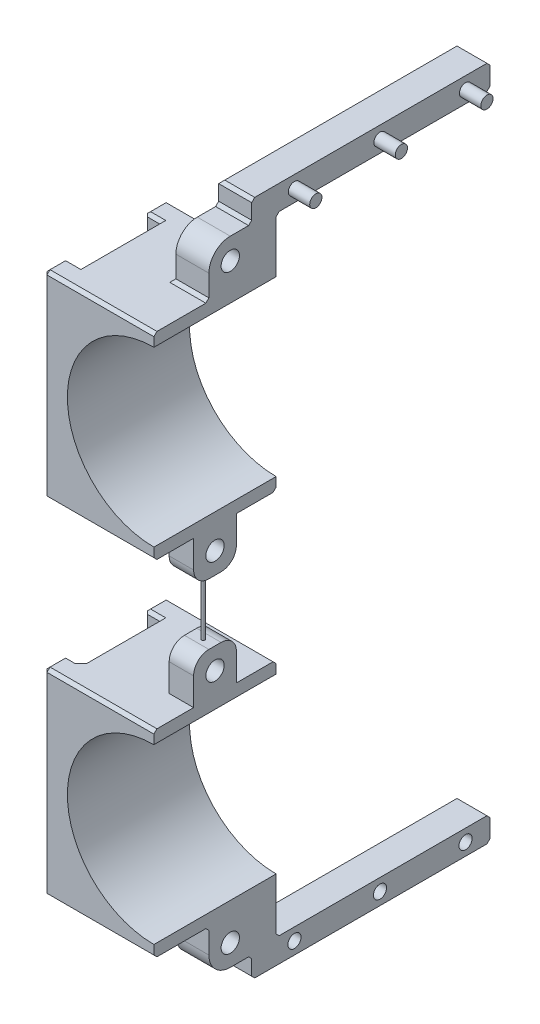
SolidWorks part; units mm, degrees
ref_plane "Front Plane" through (0, 0, 0) normal (0, 0, 1) x (1, 0, 0)
ref_plane "Top Plane" through (0, 0, 0) normal (0, 1, 0) x (1, 0, 0)
ref_plane "Right Plane" through (0, 0, 0) normal (1, 0, 0) x (0, 0, -1)
sketch "Sketch1" plane through (0, 0, 0) normal (0, 0, 1) x (1, 0, 0)
  line L0 (0, 14.16) -> (0, 16.16)
  line L1 (0, 16.16) -> (-18, 16.16)
  line L2 (-18, 16.16) -> (-18, -16.16)
  line L3 (-18, -16.16) -> (0, -16.16)
  line L4 (0, -16.16) -> (0, -14.16)
  arc A0 (0, 14.16) -> (0, -14.16) centre (0, 0) ccw
  dimension "D1" = 14.16
  dimension "D2" = 2
  dimension "D3" = 2
  dimension "D4" = 18
  dimension "D5" = 32.32
extrude "Boss-Extrude1" add sketch "Sketch1" along normal blind 20 contours A0 L4 L3 L2 L1 L0
sketch "Sketch3" plane through (0, -16.16, 0) normal (0, -1, 0) x (1, 0, 0)
  line L1 (0, 0) -> (-5.4, 0)
  line L2 (0, 0) -> (0, 4)
  line L3 (0, 4) -> (-5.4, 4)
  line L4 (-5.4, 0) -> (-5.4, 4)
  dimension "D1" = 4
  dimension "D2" = 5.4
extrude "Boss-Extrude2" add sketch "Sketch3" along normal blind 11 contours L3 L4 L1 L2
sketch "Sketch4" plane through (0, 0, 0) normal (0, 0, -1) x (-1, 0, 0)
  line L0 (0, -27.16) -> (0, -14.16) construction
  line L1 (5.4, -27.16) -> (0, -27.16)
  line L2 (5.4, -27.16) -> (5.4, -23.16)
  line L3 (5.4, -23.16) -> (0, -23.16)
  line L4 (0, -27.16) -> (0, -23.16)
  dimension "D1" = 4
extrude "Boss-Extrude3" add sketch "Sketch4" along normal blind 35
chamfer "Chamfer1" distance 0.5 angle 45 10 edges at (-2.7, -27.16, 4) (-2.7, -27.16, -35) (-2.7, -23.16, -35) (-9, 16.16, 0) (-18, 0, 0) (-9, -16.16, 20) (-9, 16.16, 20) (-18, 16.16, 10) (-18, 0, 20) (-18, -16.16, 10)
sketch "Sketch7" plane through (0, 16.16, 0) normal (0, 1, 0) x (1, 0, 0)
  line L0 (0, -19.5) -> (0, -0.5) construction
  line L1 (0, -6.5) -> (-4, -6.5)
  line L2 (0, -6.5) -> (0, -13.5)
  line L3 (0, -13.5) -> (-4, -13.5)
  line L4 (-4, -6.5) -> (-4, -13.5)
  line L5 (0, -0.5) -> (-17.5, -0.5) construction
  dimension "D1" = 6
  dimension "D2" = 7
  dimension "D3" = 4
extrude "Boss-Extrude4" add sketch "Sketch7" along normal blind 7
fillet "Fillet1" radius 2.5 2 edges at (-2, 23.16, 6.5) (-2, 23.16, 13.5)
sketch "Sketch11" plane through (0, 0, 4) normal (0, 0, 1) x (1, 0, 0)
  line L0 (-5.4, -16.16) -> (0, -16.16)
  line L4 (-5.4, -16.16) -> (-5.4, -23.66)
  line L5 (-5.4, -26.66) -> (-5.4, -16.16) construction
  line L6 (-5.4, -23.66) -> (0, -23.66)
  line L7 (0, -26.66) -> (0, -16.16) construction
  line L8 (0, -23.66) -> (0, -16.16)
  dimension "D1" = 7.5
extrude "Boss-Extrude5" add sketch "Sketch11" along normal blind 7
chamfer "Chamfer3" distance 0.5 angle 45 4 edges at (-5.4, -25.16, -35) (-5.4, -27.16, -15.5) (-2.7, -16.16, 11) (-2.7, -23.66, 4)
chamfer "Chamfer5" distance 0.5 angle 45 5 edges at (-5.4, -16.16, 5.75) (-5.4, -19.66, 0) (-11.45, -16.16, 0) (-5.4, -23.16, -17.25) (-2.7, -23.16, 0)
sketch "Sketch15" plane through (0, 23.16, 0) normal (0, 1, 0) x (1, 0, 0)
  circle A0 centre (-1.9153, -10.0073) radius 0.2766
extrude "Boss-Extrude6" add sketch "Sketch15" along normal blind 5
sketch "Sketch32" plane through (-18, 0, 0) normal (-1, 0, 0) x (0, 0, 1)
  line L0 (0.5, 16.16) -> (19.5, 16.16) construction
  line L1 (3.55, 16.16) -> (16.45, 16.16)
  line L2 (3.55, 16.16) -> (3.55, -16.16)
  line L3 (3.55, -16.16) -> (16.45, -16.16)
  line L4 (16.45, 16.16) -> (16.45, -16.16)
  line L5 (19.5, -16.16) -> (0.5, -16.16) construction
  line L6 (3.55, 0) -> (0, 0) construction
  line L7 (16.45, 0) -> (20, 0) construction
  line L8 (20, 15.66) -> (20, -15.66) construction
  dimension "D1" = 12.9
extrude "Cut-Extrude1" cut sketch "Sketch32" against normal blind 2.5
mirror "Mirror21" about plane through (-1.9153, 28.16, 10.0073) normal (0, 1, 0) of bodies 124 116
hole_wizard "CBORE for M6 Hexagon head bolts-Full thread-grade C3" positions "Sketch18" profile "Sketch19" counterbore size "M6" standard "GB" end condition through all
sketch "Sketch18" plane through (-5.4, 0, 0) normal (-1, 0, 0) x (0, 0, 1)
  line L5 (11, -16.66) -> (4, -16.66)
  line L6 (11, -16.66) -> (0.5, -16.66) construction
  line L12 (7.5, -16.66) -> (7.5, -23.66) construction
  line L13 (11, -23.66) -> (4.5, -23.66) construction
  line L14 (6.5, 16.16) -> (13.5, 16.16)
  line L16 (10, 16.16) -> (10, 23.16)
  line L17 (9, 23.16) -> (11, 23.16) construction
  line L18 (11, -16.66) -> (11, -23.66) construction
  point P0 (7.5, -20.16)
  point P2 (10, 19.66)
  dimension "D1" = 3.5
  dimension "D2" = 3.5
sketch "Sketch19" plane through (-5.4, -20.16, 7.5) normal (0, 1, 0) x (0, 0, 1)
  line L0 (0, 0) -> (0, 5.4)
  line L1 (0, 5.4) -> (1.5, 5.4)
  line L3 (1.5, 5.4) -> (1.5, 3)
  line L4 (1.5, 3) -> (3, 3)
  line L5 (3, 3) -> (3, 0)
  line L7 (3, 0) -> (0, 0)
  line L11 (0, -6.35) -> (0, 107.95) construction
  dimension "Thru Hole Dia." = 3
  dimension "Thru Hole Depth" = 5.4
  dimension "C'Bore Dia." = 6
  dimension "C'Bore Depth" = 3
hole_wizard "Ø1.0mm Dowel Hole1" positions "Sketch20" profile "Sketch21" hole size "Ø1.0" standard "GB" end condition through all
sketch "Sketch20" plane through (-4, 0, 0) normal (-1, 0, 0) x (0, 0, 1)
  line L0 (11, 72.98) -> (4, 72.98)
  line L1 (11, 72.98) -> (0.5, 72.98) construction
  line L7 (10, 40.16) -> (10, 33.16)
  line L8 (6.5, 40.16) -> (13.5, 40.16) construction
  line L9 (9, 33.16) -> (11, 33.16) construction
  line L10 (7.5, 72.98) -> (7.5, 79.98) construction
  line L11 (11, 79.98) -> (4.5, 79.98) construction
  point P0 (10, 36.66)
  point P2 (7.5, 76.48)
  point P30 (10, 36.66)
  dimension "D1" = 3.5
sketch "Sketch21" plane through (-4, 36.66, 10) normal (0, 1, 0) x (0, 0, 1)
  line L0 (0, 0) -> (0, 4)
  line L1 (0, 4) -> (1.5, 4)
  line L2 (1.5, 4) -> (1.5, 0)
  line L5 (1.5, 0) -> (0, 0)
  line L11 (0, -6.35) -> (0, 107.95) construction
  dimension "Thru Hole Dia." = 3
  dimension "Thru Hole Depth" = 4
hole_wizard "Ø1.0mm Dowel Hole2" positions "Sketch24" profile "Sketch25" hole size "Ø1.0" standard "GB" end condition through all
sketch "Sketch24" plane through (-5.4, 0, 0) normal (-1, 0, 0) x (0, 0, 1)
  line L0 (11, 72.98) -> (4, 72.98)
  line L1 (11, 72.98) -> (0.5, 72.98) construction
  line L5 (7.5, 72.98) -> (7.5, 79.98)
  line L6 (11, 79.98) -> (4.5, 79.98) construction
  point P0 (7.5, 76.48)
  dimension "D1" = 7
sketch "Sketch25" plane through (-5.4, 76.48, 7.5) normal (0, 1, 0) x (0, 0, 1)
  line L0 (0, 0) -> (0, 5.4)
  line L1 (0, 5.4) -> (1.5, 5.4)
  line L2 (1.5, 5.4) -> (1.5, 0)
  line L5 (1.5, 0) -> (0, 0)
  line L11 (0, -6.35) -> (0, 107.95) construction
  dimension "Thru Hole Dia." = 3
  dimension "Thru Hole Depth" = 5.4
hole_wizard "Ø1.0mm Dowel Hole3" positions "Sketch28" profile "Sketch29" hole size "Ø1.0" standard "GB"
sketch "Sketch28" plane through (0, 0, 0) normal (1, 0, 0) x (0, 0, -1)
  line L0 (3, -23.16) -> (3, -27.16)
  line L1 (34.5, -23.16) -> (0.5, -23.16) construction
  line L2 (34.5, -27.16) -> (-3.5, -27.16) construction
  line L4 (31, -23.16) -> (31, -27.16)
  line L6 (35, -23.66) -> (35, -26.66) construction
  line L7 (-4, -26.66) -> (-4, -24.16) construction
  line L9 (17, -23.16) -> (17, -27.16)
  point P0 (3, -25.16)
  point P2 (31, -25.16)
  point P17 (3, -25.16)
  point P18 (31, -25.16)
  point P29 (17, -25.16)
  dimension "D1" = 4
  dimension "D2" = 7
  dimension "D3" = 14
sketch "Sketch29" plane through (0, -25.16, -3) normal (0, 1, 0) x (0, 0, -1)
  line L0 (0, 0) -> (0, 4)
  line L1 (0, 4) -> (1.075, 4)
  line L2 (1.075, 4) -> (1.075, 0)
  line L5 (1.075, 0) -> (0, 0)
  line L10 (0, 4) -> (-1.075, 4) construction
  line L11 (0, -6.35) -> (0, 107.95) construction
  dimension "Hole Dia." = 2.15
  dimension "Hole Depth" = 4
  dimension "Drill Angle" = 180
sketch "Sketch30" plane through (0, 0, 0) normal (1, 0, 0) x (0, 0, -1)
  line L0 (3, 83.48) -> (3, 79.48) construction
  line L1 (34.5, 83.48) -> (-3.5, 83.48) construction
  line L2 (34.5, 79.48) -> (0.5, 79.48) construction
  line L3 (17, 83.48) -> (17, 79.48) construction
  line L4 (31, 83.48) -> (31, 79.48) construction
  line L5 (-4, 82.98) -> (-4, 80.48) construction
  line L6 (35, 79.98) -> (35, 82.98) construction
  circle A0 centre (3, 81.48) radius 1
  circle A1 centre (17, 81.48) radius 1
  circle A2 centre (31, 81.48) radius 1
  dimension "D4" = 2
  dimension "D5" = 2
  dimension "D6" = 2
  dimension "D1" = 7
  dimension "D2" = 4
  dimension "D3" = 14
extrude "Boss-Extrude7" add sketch "Sketch30" along normal blind 3.5
chamfer "Chamfer6" distance 0.5 angle 45 19 edges at (-16.5, 40.16, 16.45) (-15.5, 40.16, 10) (-16.5, 40.16, 3.55) (-16.5, 72.48, 3.55) (-16.5, 72.48, 16.45) (-15.5, 72.48, 10) (-16.5, -16.16, 16.45) (-16.5, -16.16, 3.55) (-15.5, -16.16, 10) (-15.5, 0, 16.45) (-17.75, -15.91, 16.45) (-18, 0, 16.45) (-17.75, 15.91, 16.45) (-16.5, 16.16, 16.45) (-16.5, 16.16, 3.55) (-15.5, 16.16, 10) (-18, 0, 3.55) (-18, 56.32, 3.55) (-18, 56.32, 16.45)
fillet "Fillet2" radius 3.5 2 edges at (-2.7, -23.66, 11) (-2.7, 79.98, 11)
